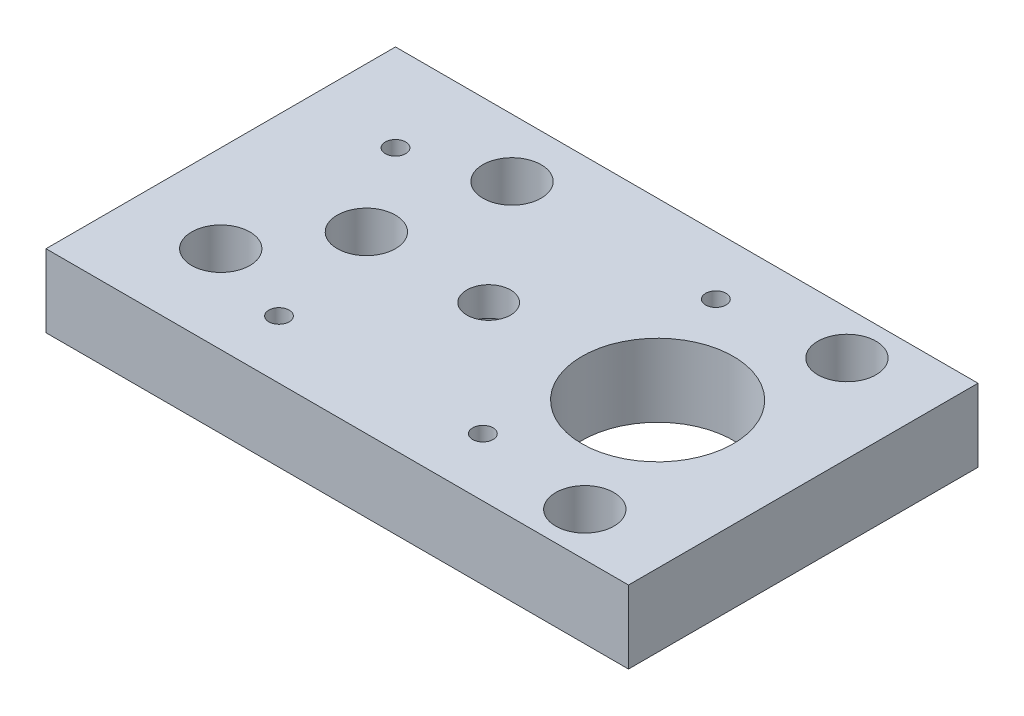
SolidWorks part; units mm, degrees
ref_plane "前视基准面" through (0, 0, 0) normal (0, 0, 1) x (1, 0, 0)
ref_plane "上视基准面" through (0, 0, 0) normal (0, 1, 0) x (1, 0, 0)
ref_plane "右视基准面" through (0, 0, 0) normal (1, 0, 0) x (0, 0, -1)
other "Configuration Table"
sketch "草图1" plane through (0, 0, 0) normal (0, 1, 0) x (1, 0, 0)
  line L0 (7.8359, -6) -> (30.681, -6) construction
  line L1 (0, 0) -> (20, 0)
  line L2 (0, 0) -> (0, -12)
  line L3 (0, -12) -> (20, -12)
  line L4 (20, 0) -> (20, -12)
  circle A3 centre (9.2, -6) radius 1.6
  circle A5 centre (15, -6) radius 2.6
  circle A6 centre (9.2, -6) radius 0.75
  circle A7 centre (5, -6) radius 1
  point P5 (5, -6)
  dimension "D4" = 5.8
  dimension "D6" = 3.2
  dimension "D8" = 2
  dimension "D11" = 5.2
  dimension "D13" = 1.5
  dimension "D2" = 5
  dimension "D3" = 4.2
  dimension "D5" = 10
  dimension "D7" = 20
  dimension "D9" = 6
  dimension "D10" = 5
  dimension "D12" = 12
extrude "凸台-拉伸1" add sketch "草图1" along normal blind 2.5 contours L4 L3 L2 L1 | A3 | A5 | A7
extrude "凸台-拉伸2" add sketch "草图1<5>" against normal blind 1 from surface contours A3 | A6 starting at face at (10, 2.5, 6)
sketch "草图1<5>" plane through (0, 0, 0) normal (0, 1, 0) x (1, 0, 0) same geometry as "草图1"
sketch "草图3" plane through (0, 2.5, 0) normal (0, 1, 0) x (1, 0, 0)
  line L0 (0, 0) -> (0, -12) construction
  line L1 (0, 0) -> (20, 0) construction
  line L2 (0, -12) -> (20, -12) construction
  line L3 (20, 0) -> (20, -12) construction
  circle A0 centre (6, -2) radius 1
  circle A1 centre (3, -9) radius 1
  circle A2 centre (17, -1.5) radius 1
  circle A3 centre (17, -10.5) radius 1
  circle A4 centre (3, -9) radius 0.7
  circle A5 centre (6, -2) radius 0.7
  circle A6 centre (17, -1.5) radius 0.7
  circle A7 centre (17, -10.5) radius 0.7
  circle A11 centre (3, -3) radius 0.35
  circle A12 centre (6, -10) radius 0.35
  circle A13 centre (13, -10) radius 0.35
  circle A14 centre (13, -2) radius 0.35
  circle A21 centre (3, -9) radius 0.35 construction
  dimension "D1" = 1.4
  dimension "D2" = 2
  dimension "D3" = 0.7
  dimension "D4" = 3
  dimension "D5" = 3
  dimension "D6" = 2
  dimension "D7" = 6
  dimension "D8" = 7
  dimension "D9" = 2
  dimension "D10" = 7
  dimension "D11" = 2
extrude "切除-拉伸1" cut sketch "草图3" against normal through all contours A5 | A4 | A6 | A7 | A12 | A11 | A14 | A13
extrude "切除-拉伸2" cut sketch "草图3<3>" against normal blind 1.5 contours A0 | A1 | A3 | A2
sketch "草图3<3>" plane through (0, 2.5, 0) normal (0, 1, 0) x (1, 0, 0) same geometry as "草图3"
